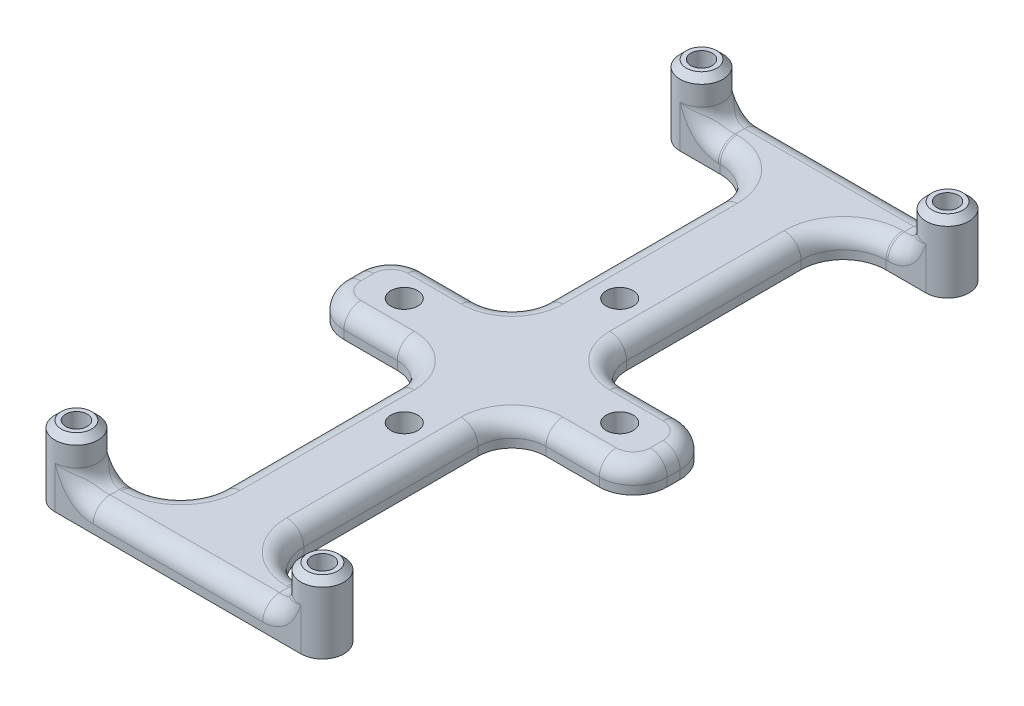
SolidWorks part; units mm, degrees
ref_plane "Front Plane" through (0, 0, 0) normal (0, 0, 1) x (1, 0, 0)
ref_plane "Top Plane" through (0, 0, 0) normal (0, 1, 0) x (1, 0, 0)
ref_plane "Right Plane" through (0, 0, 0) normal (1, 0, 0) x (0, 0, -1)
sketch "Sketch1" plane through (0, 0, 0) normal (0, 1, 0) x (1, 0, 0)
  line L1 (-4.7625, -34.305) -> (4.7625, -34.305)
  line L2 (-4.7625, -34.305) -> (-4.7625, 34.305)
  line L3 (-4.7625, 34.305) -> (4.7625, 34.305)
  line L4 (4.7625, -34.305) -> (4.7625, 34.305)
  line L5 (-4.7625, -34.305) -> (4.7625, 34.305) construction
  line L6 (-4.7625, 34.305) -> (4.7625, -34.305) construction
  line L7 (-14.5, 39.385) -> (14.5, 39.385)
  line L9 (-14.5, 34.305) -> (14.5, 34.305)
  line L11 (-14.5, 39.385) -> (14.5, 34.305) construction
  line L12 (-14.5, 34.305) -> (14.5, 39.385) construction
  line L13 (-14.5, -39.385) -> (14.5, -39.385)
  line L15 (-14.5, -34.305) -> (14.5, -34.305)
  line L17 (-14.5, -39.385) -> (14.5, -34.305) construction
  line L18 (-14.5, -34.305) -> (14.5, -39.385) construction
  arc A2 (-14.5, 34.305) -> (-14.5, 39.385) centre (-14.5, 36.845) cw
  arc A3 (14.5, 34.305) -> (14.5, 39.385) centre (14.5, 36.845) ccw
  arc A4 (-14.5, -39.385) -> (-14.5, -34.305) centre (-14.5, -36.845) cw
  arc A5 (14.5, -39.385) -> (14.5, -34.305) centre (14.5, -36.845) ccw
  point P0 (0, 0)
  point P6 (0, 36.845)
  point P11 (0, -36.845)
  dimension "D4" = 29
  dimension "D1" = 9.525
  dimension "D2" = 5.08
  dimension "D3" = 5.08
  dimension "D5" = 73.69
extrude "Boss-Extrude1" add sketch "Sketch1" along normal blind 3 contours L13 A5 L15 L1 A4 | L1 L4 L3 L2 | L9 A3 L7 A2 L3 region at (0, 0, 0) region at (0, 0, 36.845) region at (0, 0, -36.845)
sketch "Sketch2" plane through (0, 3, 0) normal (0, 1, 0) x (1, 0, 0)
  line L0 (0, 12.7) -> (0, -12.7) construction
  circle A0 centre (0, 12.7) radius 1.5875
  circle A1 centre (0, -12.7) radius 1.5875
  dimension "D2" = 3.175
  dimension "D3" = 3.175
  dimension "D1" = 25.4
extrude "Cut-Extrude1" cut sketch "Sketch2" against normal through all
sketch "Sketch3" plane through (0, 3, 0) normal (0, 1, 0) x (1, 0, 0)
  circle A0 centre (-14.5, 36.845) radius 2.54
  circle A1 centre (14.5, 36.845) radius 2.54
  circle A2 centre (14.5, -36.845) radius 2.54
  circle A3 centre (-14.5, -36.845) radius 2.54
  arc A4 (-14.5, 39.385) -> (-14.5, 34.305) centre (-14.5, 36.845) ccw construction
  arc A5 (14.5, 34.305) -> (14.5, 39.385) centre (14.5, 36.845) ccw construction
  arc A6 (-14.5, -34.305) -> (-14.5, -39.385) centre (-14.5, -36.845) ccw construction
  arc A7 (14.5, -39.385) -> (14.5, -34.305) centre (14.5, -36.845) ccw construction
extrude "Boss-Extrude2" add sketch "Sketch3" along normal blind 5.08
sketch "Sketch4" plane through (0, 8.08, 0) normal (0, 1, 0) x (1, 0, 0)
  circle A0 centre (-14.5, 36.845) radius 1.27
  circle A1 centre (14.5, 36.845) radius 1.27
  circle A2 centre (14.5, -36.845) radius 1.27
  circle A3 centre (-14.5, -36.845) radius 1.27
  dimension "D1" = 2.54
  dimension "D2" = 2.54
  dimension "D3" = 2.54
  dimension "D4" = 2.54
extrude "Cut-Extrude2" cut sketch "Sketch4" against normal blind 3.2004
sketch "Sketch5" plane through (0, 4.8796, 0) normal (0, 1, 0) x (1, 0, 0)
  circle A0 centre (-14.5, 36.845) radius 0.875
  circle A1 centre (14.5, 36.845) radius 0.875
  circle A2 centre (14.5, -36.845) radius 0.875
  circle A3 centre (-14.5, -36.845) radius 0.875
  dimension "D1" = 1.75
  dimension "D2" = 1.75
  dimension "D3" = 1.75
  dimension "D4" = 1.75
extrude "Cut-Extrude3" cut sketch "Sketch5" against normal through all
chamfer "Chamfer1" distance 0.75 angle 45 4 edges at (-14.5, 8.08, -34.305) (14.5, 8.08, -34.305) (14.5, 8.08, 39.385) (-14.5, 8.08, 39.385)
fillet "Fillet1" radius 5 4 edges at (-4.7625, 1.5, -34.305) (4.7625, 1.5, -34.305) (-4.7625, 1.5, 34.305) (4.7625, 1.5, 34.305)
fillet "Fillet2" radius 2 4 edges at (-11.96, 3, 36.845) (11.96, 3, 36.845) (11.96, 3, -36.845) (-11.96, 3, -36.845)
sketch "Sketch6" plane through (0, 3, 0) normal (0, 1, 0) x (1, 0, 0)
  line L1 (-19.05, -4.7625) -> (19.05, -4.7625)
  line L2 (-19.05, -4.7625) -> (-19.05, 4.7625)
  line L3 (-19.05, 4.7625) -> (19.05, 4.7625)
  line L4 (19.05, -4.7625) -> (19.05, 4.7625)
  line L5 (-19.05, -4.7625) -> (19.05, 4.7625) construction
  line L6 (-19.05, 4.7625) -> (19.05, -4.7625) construction
  point P0 (0, 0)
  dimension "D1" = 9.525
  dimension "D2" = 38.1
extrude "Boss-Extrude3" add sketch "Sketch6" against normal up to surface (3 mm away) up to face at (-14.5, 0, 37.72)
fillet "Fillet3" radius 4 8 edges at (-4.7625, 1.5, -4.7625) (-19.05, 1.5, -4.7625) (-19.05, 1.5, 4.7625) (-4.7625, 1.5, 4.7625) (4.7625, 1.5, 4.7625) (4.7625, 1.5, -4.7625) (19.05, 1.5, 4.7625) (19.05, 1.5, -4.7625)
sketch "Sketch7" plane through (0, 3, 0) normal (0, 1, 0) x (1, 0, 0)
  line L0 (-12.7, 0) -> (12.7, 0) construction
  circle A0 centre (-12.7, 0) radius 1.5875
  circle A1 centre (12.7, 0) radius 1.5875
  dimension "D2" = 3.175
  dimension "D3" = 3.175
  dimension "D1" = 25.4
extrude "Cut-Extrude4" cut sketch "Sketch7" against normal through all
fillet "Fillet4" radius 2 30 edges at (11.737, 3.1613, 34.305) (10.2498, 3, 34.305) (6.227, 3, 32.8405) (4.7625, 3, 19.0337) (11.737, 3.1613, -34.305) (10.2498, 3, -34.305) (6.227, 3, -32.8405) (4.7625, 3, -19.0337) (5.9341, 3, -5.9341) (11.9062, 3, -4.7625) (17.8784, 3, -3.5909) (19.05, 3, 0) (17.8784, 3, 3.5909) (11.9062, 3, 4.7625) (-11.737, 3.1613, 34.305) (-10.2498, 3, 34.305) (-6.227, 3, 32.8405) (-11.737, 3.1613, -34.305) (-10.2498, 3, -34.305) (-6.227, 3, -32.8405) (-4.7625, 3, -19.0337) (-5.9341, 3, -5.9341) (-11.9063, 3, -4.7625) (-17.8784, 3, -3.5909) (-19.05, 3, 0) (-17.8784, 3, 3.5909) (-11.9063, 3, 4.7625) (-5.9341, 3, 5.9341) (5.9341, 3, 5.9341) (-4.7625, 3, 19.0337)
fillet "Fillet5" radius 2 6 edges at (-11.737, 3.1613, -39.385) (11.737, 3.1613, -39.385) (-11.737, 3.1613, 39.385) (11.737, 3.1613, 39.385) (0, 3, -39.385) (0, 3, 39.385)
